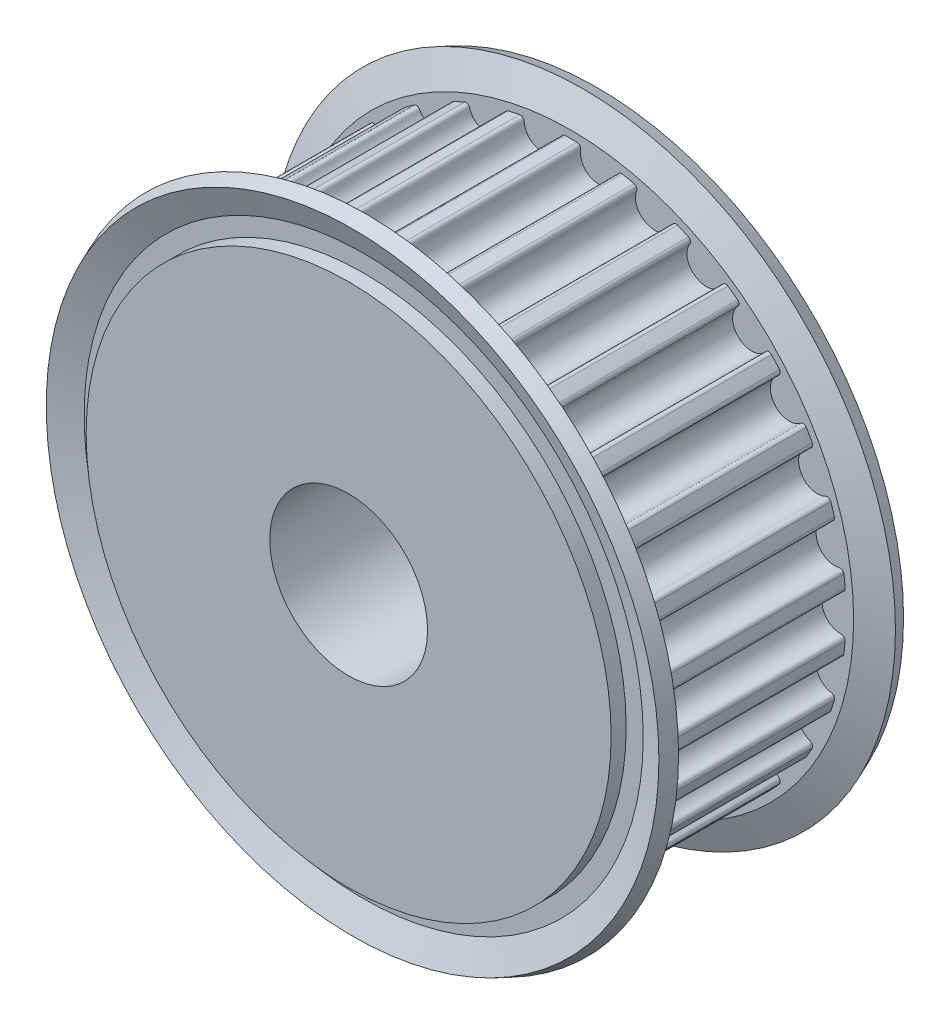
SolidWorks part; units mm, degrees
ref_plane "前视基准面" through (0, 0, 0) normal (0, 0, 1) x (1, 0, 0)
ref_plane "上视基准面" through (0, 0, 0) normal (0, 1, 0) x (1, 0, 0)
ref_plane "右视基准面" through (0, 0, 0) normal (1, 0, 0) x (0, 0, -1)
ref_axis "基准轴1" through (0, 0, 55) along (0, 0, -1)
sketch "SketchRevolveGearBelt01Pulley" plane through (0, 0, 0) normal (1, 0, 0) x (0, 0, -1)
  line L0 (0, 0) -> (1, 0) construction
  line L1 (6.4008, 0) -> (6.4008, 13.3069)
  line L2 (6.4008, 13.3069) -> (5.6388, 13.3069)
  line L3 (5.6388, 13.3069) -> (5.6388, 14.1713)
  line L4 (5.6388, 14.1713) -> (6.2015, 15.5299)
  line L5 (6.2015, 15.5299) -> (5.4975, 15.8215)
  line L6 (5.4975, 15.8215) -> (4.8768, 14.3229)
  line L7 (4.8768, 14.3229) -> (4.8768, 13.9419)
  line L8 (4.8768, 13.9419) -> (-4.8768, 13.9419)
  line L9 (-4.8768, 13.9419) -> (-4.8768, 14.3229)
  line L10 (-4.8768, 14.3229) -> (-5.4975, 15.8215)
  line L11 (-5.4975, 15.8215) -> (-6.2015, 15.5299)
  line L12 (-6.2015, 15.5299) -> (-5.6388, 14.1713)
  line L13 (-5.6388, 14.1713) -> (-5.6388, 13.3069)
  line L14 (-5.6388, 13.3069) -> (-6.4008, 13.3069)
  line L15 (-6.4008, 13.3069) -> (-6.4008, 0)
  line L16 (-6.4008, 0) -> (6.4008, 0)
  dimension "GearBeltFlange1OutsideLength" = 0.8644
  dimension "GearBeltFlange1X" = 0.5627
  dimension "GearBeltFlange1Y" = 1.3586
  dimension "GearBeltFlangeThickness" = 0.762
  dimension "GearBeltFlangeInside" = 0.381
  dimension "GearBeltOutsideDiameter" = 13.9419
  dimension "GearBeltFlange2X" = 0.5627
revolve "GearBelt01Pulley" add sketch "SketchRevolveGearBelt01Pulley" angle 360 about L0 other way angle 360
sketch "SketchToothGearBelt01Pulley" plane through (0, 0, 0) normal (0, 0, 1) x (1, 0, 0)
  arc A0 (13.8935, 1.162) -> (13.8935, -1.162) centre (0, 0) cw
  spline S0 degree 3 poles (13.8935, -1.162) (13.8944, -1.1516) (13.8944, -1.1357) (13.8918, -1.1148) (13.8886, -1.0994) (13.8841, -1.0843) (13.8784, -1.0695) (13.8714, -1.0553) (13.8634, -1.0418) (13.8542, -1.0289) (13.844, -1.0168) (13.8329, -1.0057) (13.8209, -0.9954) (13.808, -0.9862) (13.7945, -0.9781) (13.7803, -0.9712) (13.7656, -0.9654) (13.7505, -0.9609) (13.735, -0.9576) (13.7194, -0.9556) (13.6903, -0.9547) (13.6423, -0.9556) (13.5752, -0.953) (13.503, -0.9442) (13.4317, -0.9299) (13.3617, -0.91) (13.2935, -0.8847) (13.2275, -0.8541) (13.1641, -0.8184) (13.1036, -0.7779) (13.0466, -0.7328) (12.9932, -0.6834) (12.9439, -0.6299) (12.8989, -0.5727) (12.8585, -0.5122) (12.8231, -0.4487) (12.7926, -0.3826) (12.7675, -0.3143) (12.7478, -0.2443) (12.7336, -0.1729) (12.725, -0.1007) (12.7231, -0.0476) (12.7232, -0.014) (12.7232, 0) (12.7232, 0.014) (12.7231, 0.0476) (12.725, 0.1007) (12.7336, 0.1729) (12.7478, 0.2443) (12.7675, 0.3143) (12.7926, 0.3826) (12.8231, 0.4487) (12.8585, 0.5122) (12.8989, 0.5727) (12.9439, 0.6299) (12.9932, 0.6834) (13.0466, 0.7328) (13.1036, 0.7779) (13.1641, 0.8184) (13.2275, 0.8541) (13.2935, 0.8847) (13.3617, 0.91) (13.4317, 0.9299) (13.503, 0.9442) (13.5752, 0.953) (13.6423, 0.9556) (13.6903, 0.9547) (13.7194, 0.9556) (13.735, 0.9576) (13.7505, 0.9609) (13.7656, 0.9654) (13.7803, 0.9712) (13.7945, 0.9781) (13.808, 0.9862) (13.8209, 0.9954) (13.8329, 1.0057) (13.844, 1.0168) (13.8542, 1.0289) (13.8634, 1.0418) (13.8714, 1.0553) (13.8784, 1.0695) (13.8841, 1.0843) (13.8886, 1.0994) (13.8918, 1.1148) (13.8944, 1.1357) (13.8944, 1.1516) (13.8935, 1.162) knots 0 0 0 0 0.008513 0.012769 0.017025 0.021281 0.025538 0.029794 0.03405 0.038306 0.042563 0.046819 0.051075 0.055331 0.059588 0.063844 0.0681 0.072356 0.076613 0.080869 0.085125 0.100157 0.119771 0.139386 0.159 0.178614 0.198229 0.217843 0.237457 0.257071 0.276686 0.2963 0.315914 0.335529 0.355143 0.374757 0.394372 0.413986 0.4336 0.453214 0.472829 0.492443 0.496222 0.5 0.503778 0.507557 0.527171 0.546786 0.5664 0.586014 0.605628 0.625243 0.644857 0.664471 0.684086 0.7037 0.723314 0.742929 0.762543 0.782157 0.801771 0.821386 0.841 0.860614 0.880229 0.899843 0.914875 0.919131 0.923387 0.927644 0.9319 0.936156 0.940412 0.944669 0.948925 0.953181 0.957437 0.961694 0.96595 0.970206 0.974462 0.978719 0.982975 0.987231 0.991487 1 1 1 1
extrude "ToothExtrudeCutGearBelt01Pulley" cut sketch "SketchToothGearBelt01Pulley" against normal blind 4.8768 and the other way blind 4.8768
pattern_circular "PatternGearBelt01Pulley" count 30 every 12 about axis through (0, 0, 55) along (0, 0, -1) of "ToothExtrudeCutGearBelt01Pulley"
sketch "BoreRevolveSketch" plane through (0, 0, 0) normal (1, 0, 0) x (0, 0, -1)
  line L0 (0, 0) -> (1, 0) construction
  line L1 (-6.4008, 0) -> (6.4008, 0)
  line L2 (6.4008, 0) -> (6.4008, 4)
  line L3 (6.4008, 4) -> (-6.4008, 4)
  line L4 (-6.4008, 4) -> (-6.4008, 0)
  dimension "TaperSide1" = 4
  dimension "TaperSide2" = 4
revolve "BoreRevolveCut" cut sketch "BoreRevolveSketch" angle 360 about L0
sketch "AuxiliarySketchGearBelt01Pulley" plane through (0, 0, 0) normal (0, 0, 1) x (1, 0, 0)
  circle A0 centre (0, 0) radius 14.3229 construction
  dimension "PitchDiameter" = 28.6458
